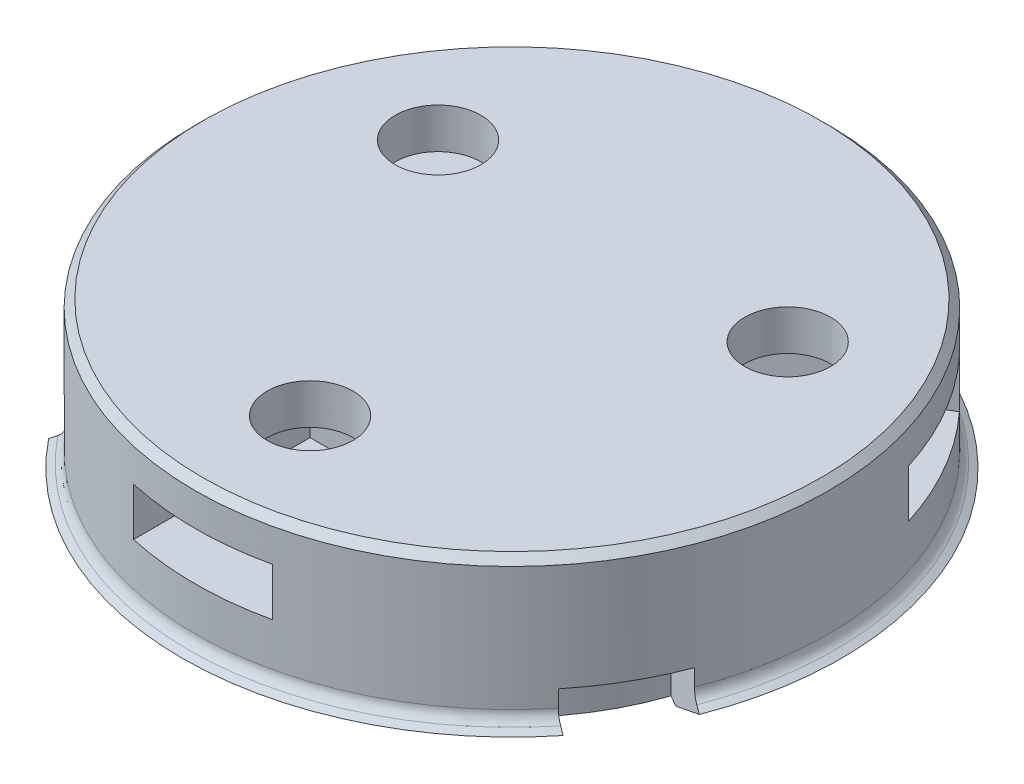
SolidWorks part; units mm, degrees
ref_plane "Front Plane" through (0, 0, 0) normal (0, 0, 1) x (1, 0, 0)
ref_plane "Top Plane" through (0, 0, 0) normal (0, 1, 0) x (1, 0, 0)
ref_plane "Right Plane" through (0, 0, 0) normal (1, 0, 0) x (0, 0, -1)
sketch "Sketch1" plane through (0, 0, 0) normal (0, 1, 0) x (1, 0, 0)
  circle A0 centre (0, 0) radius 10.05
  dimension "D1" = 20.1
extrude "Boss-Extrude1" add sketch "Sketch1" along normal blind 1.746
sketch "Sketch2" plane through (0, 1.746, 0) normal (0, 1, 0) x (1, 0, 0)
  circle A0 centre (0, 0) radius 12.55
  dimension "D1" = 25.1
extrude "Boss-Extrude2" add sketch "Sketch2" along normal blind 4
sketch "Sketch3" plane through (0, 0, 0) normal (0, -1, 0) x (1, 0, 0)
  circle A0 centre (0, 0) radius 3.25
  dimension "D1" = 6.5
extrude "Cut-Extrude1" cut sketch "Sketch3" against normal through all
sketch "Sketch4" plane through (0, 0, 0) normal (0, -1, 0) x (1, 0, 0)
  line L0 (0, 0) -> (0, 12.55) construction
  line L1 (0, 0) -> (0, 6.5) construction
  line L2 (0, 0) -> (5.6292, -3.25) construction
  circle A0 centre (0, 0) radius 12.55 construction
  circle A1 centre (0, 6.5) radius 2.525
  circle A2 centre (5.6292, -3.25) radius 2.525
  circle A3 centre (-5.6292, -3.25) radius 2.525
  dimension "D1" = 5.05
  dimension "D2" = 6.5
  dimension "D4" = 120
  dimension "D3" = 3
extrude "Cut-Extrude2" cut sketch "Sketch4" against normal blind 2.5
sketch "Sketch5" plane through (0, 2.5, 0) normal (0, -1, 0) x (1, 0, 0)
  circle A0 centre (0, 6.5) radius 1.75
  circle A1 centre (-5.6292, -3.25) radius 1.75
  circle A2 centre (5.6292, -3.25) radius 1.75
  dimension "D1" = 3.5
extrude "Cut-Extrude3" cut sketch "Sketch5" against normal blind 0.3
chamfer "Chamfer1" distance 0.3 angle 45 3 edges at (5.6292, 0, -5.775) (-5.6292, 0, -5.775) (0, 0, 3.975)
sketch "Sketch6" plane through (0, 0, 0) normal (0, -1, 0) x (1, 0, 0)
  line L0 (0, 0) -> (6.7117, 3.875) construction
  line L1 (0, 6.5) -> (5.6292, -3.25) construction
  line L2 (0, 0) -> (6.7117, 3.875) construction
  line L3 (0, 0) -> (0, -7.75) construction
  circle A0 centre (0, 0) radius 7.75 construction
  circle A1 centre (6.7117, 3.875) radius 1.1
  circle A2 centre (0, -7.75) radius 1.1
  circle A3 centre (-6.7117, 3.875) radius 1.1
  dimension "D1" = 15.5
  dimension "D2" = 2.2
  dimension "D3" = 3
  dimension "D4" = 120
extrude "Cut-Extrude4" cut sketch "Sketch6" against normal blind 2.5
ref_plane "Plane1" through (0, 1, 0) normal (0, -1, 0) x (-1, 0, 0)
ref_axis "Axis1" through (0, 5.746, 0) along (0, -1, 0)
sketch "Sketch10" plane through (0, 0, 0) normal (0, 0, 1) x (1, 0, 0)
  line L0 (10.05, 1.746) -> (13.5742, 1.746) construction
  line L2 (10.05, 0) -> (10.05, 1.746)
  line L3 (12.55, 1.746) -> (12.55, 5.746) construction
  line L4 (10.05, 1.746) -> (12.55, 1.746)
  line L11 (-10.05, 0) -> (10.05, 0) construction
  line L12 (10.05, 0) -> (10.55, 0) construction
  line L13 (10.55, 0) -> (13.5742, 1.746) construction
  line L14 (10.05, 0) -> (10.55, 0)
  line L15 (12.55, 1.746) -> (13.0621, 1.4504)
  line L17 (13.0621, 1.4504) -> (10.55, 0)
  dimension "D1" = 150
  dimension "D2" = 30
  dimension "D3" = 0.5
  dimension "D4" = 0.5121
revolve "Revolve1" add sketch "Sketch10" angle 360 about axis through (0, 5.746, 0) along (0, -1, 0)
sketch "Sketch7" plane through (0, 1, 0) normal (0, -1, 0) x (-1, 0, 0)
  line L0 (-1.975, 8.8903) -> (-1.975, 18.8903)
  line L1 (0, 10.0305) -> (-1.975, 8.8903) construction
  line L2 (-1.975, 8.8903) -> (-1.975, 6.6097)
  line L3 (-1.975, 6.6097) -> (0, 5.4695)
  line L4 (0, 5.4695) -> (1.975, 6.6097)
  line L5 (1.975, 6.6097) -> (1.975, 8.8903)
  line L6 (1.975, 8.8903) -> (0, 10.0305) construction
  line L7 (-1.975, 18.8903) -> (1.975, 18.8903)
  line L8 (1.975, 18.8903) -> (1.975, 8.8903)
  circle A0 centre (0, 7.75) radius 1.975 construction
  dimension "D1" = 3.95
  dimension "D2" = 10
extrude "Cut-Extrude5" cut sketch "Sketch7" against normal blind 1.7
sketch "Sketch11" plane through (0, 0, 0) normal (0, -1, 0) x (1, 0, 0)
  line L0 (1.975, -12.3936) -> (1.975, -6.6097) construction
  line L1 (-1.975, -19.854) -> (-1.975, -9.854)
  line L2 (1.975, -19.854) -> (1.975, -9.854)
  line L3 (-1.975, -6.6097) -> (-1.975, -12.3936) construction
  arc A0 (-1.975, -19.854) -> (1.975, -19.854) centre (0, 0) ccw
  arc A3 (-1.975, -9.854) -> (1.975, -9.854) centre (0, 0) ccw
  dimension "D1" = 10.05
  dimension "D2" = 10
extrude "Cut-Extrude6" cut sketch "Sketch11" against normal up to surface (2.7 mm away) up to face at (0, 2.7, -8.7265)
pattern_circular "CirPattern1" count 3 over 360 about axis through (0, 5.746, 0) along (0, -1, 0) of "Cut-Extrude5", "Cut-Extrude6"
fillet "Fillet1" radius 0.5 3 edges at (-10.8686, 1.746, -6.275) (0, 1.746, 12.55) (10.8686, 1.746, -6.275)
sketch "Sketch12" plane through (0, 5.746, 0) normal (0, 1, 0) x (1, 0, 0)
  circle A0 centre (0, 0) radius 12.55
  circle A1 centre (0, 0) radius 12.55 construction
extrude "Boss-Extrude3" add sketch "Sketch12" along normal blind 1.5
sketch "Sketch13" plane through (0, 7.246, 0) normal (0, 1, 0) x (1, 0, 0)
  circle A0 centre (0, 0) radius 8 construction
  circle A1 centre (0, -8) radius 1.7
  circle A2 centre (-6.9282, 4) radius 1.7
  circle A3 centre (6.9282, 4) radius 1.7
  point P14 (0, 0)
  dimension "D1" = 16
  dimension "D2" = 3.4
  dimension "D3" = 3
extrude "Cut-Extrude7" cut sketch "Sketch13" against normal blind 3.5
sketch "Sketch14" [suppressed] plane through (0, 3.746, 0) normal (0, 1, 0) x (1, 0, 0)
  line L0 (-2.7, -9.5588) -> (-2.7, -14.5588)
  line L1 (0, -11.1177) -> (2.7, -9.5588) construction
  line L2 (2.7, -9.5588) -> (2.7, -6.4412)
  line L3 (2.7, -6.4412) -> (0, -4.8823)
  line L4 (0, -4.8823) -> (-2.7, -6.4412)
  line L5 (-2.7, -6.4412) -> (-2.7, -9.5588)
  line L6 (-2.7, -9.5588) -> (0, -11.1177) construction
  line L7 (-2.7, -14.5588) -> (2.7, -14.5588)
  line L8 (2.7, -14.5588) -> (2.7, -9.5588)
  circle A0 centre (0, -8) radius 2.7 construction
  dimension "D1" = 5.4
  dimension "D2" = 5
extrude "Cut-Extrude8" [suppressed] cut sketch "Sketch14" along normal blind 2.7
pattern_circular "CirPattern3" [suppressed] count 3 over 360 about axis through (0, 5.746, 0) along (0, -1, 0) of bodies 113
fillet "4 Holes Fillet" [suppressed] radius 0.5
fillet "3 Holes Fillet" [suppressed] radius 0.5
sketch "Sketch15" plane through (0, 3.746, 0) normal (0, 1, 0) x (1, 0, 0)
  line L0 (-2.75, -10.75) -> (-2.75, -15.75)
  line L1 (-2.75, -10.75) -> (2.75, -10.75) construction
  line L2 (-2.75, -10.75) -> (-2.75, -5.25)
  line L3 (-2.75, -5.25) -> (2.75, -5.25)
  line L4 (2.75, -10.75) -> (2.75, -5.25)
  line L5 (-2.75, -10.75) -> (2.75, -5.25) construction
  line L6 (-2.75, -5.25) -> (2.75, -10.75) construction
  line L7 (-2.75, -15.75) -> (2.75, -15.75)
  line L8 (2.75, -15.75) -> (2.75, -10.75)
  line L9 (-15.0149, 5.4934) -> (-10.6848, 2.9934)
  line L10 (-10.6848, 2.9934) -> (-5.9216, 0.2434)
  line L11 (-3.1716, 5.0066) -> (-5.9216, 0.2434)
  line L12 (-7.9348, 7.7566) -> (-3.1716, 5.0066)
  line L13 (-7.9348, 7.7566) -> (-12.2649, 10.2566)
  line L14 (-12.2649, 10.2566) -> (-15.0149, 5.4934)
  line L15 (12.2649, 10.2566) -> (7.9348, 7.7566)
  line L16 (7.9348, 7.7566) -> (3.1716, 5.0066)
  line L17 (5.9216, 0.2434) -> (3.1716, 5.0066)
  line L18 (10.6848, 2.9934) -> (5.9216, 0.2434)
  line L19 (10.6848, 2.9934) -> (15.0149, 5.4934)
  line L20 (15.0149, 5.4934) -> (12.2649, 10.2566)
  point P0 (0, -8)
  point P22 (0, 0)
  dimension "D1" = 5
  dimension "D2" = 5.5
  dimension "D3" = 3
extrude "Cut-Extrude9" cut sketch "Sketch15" along normal blind 1.9
chamfer "Chamfer2" distance 0.3 angle 45 1 edges at (0, 7.246, 12.55)
fillet "Fillet2" [suppressed] radius 0.5
fillet "Fillet3" [suppressed] radius 0.5
